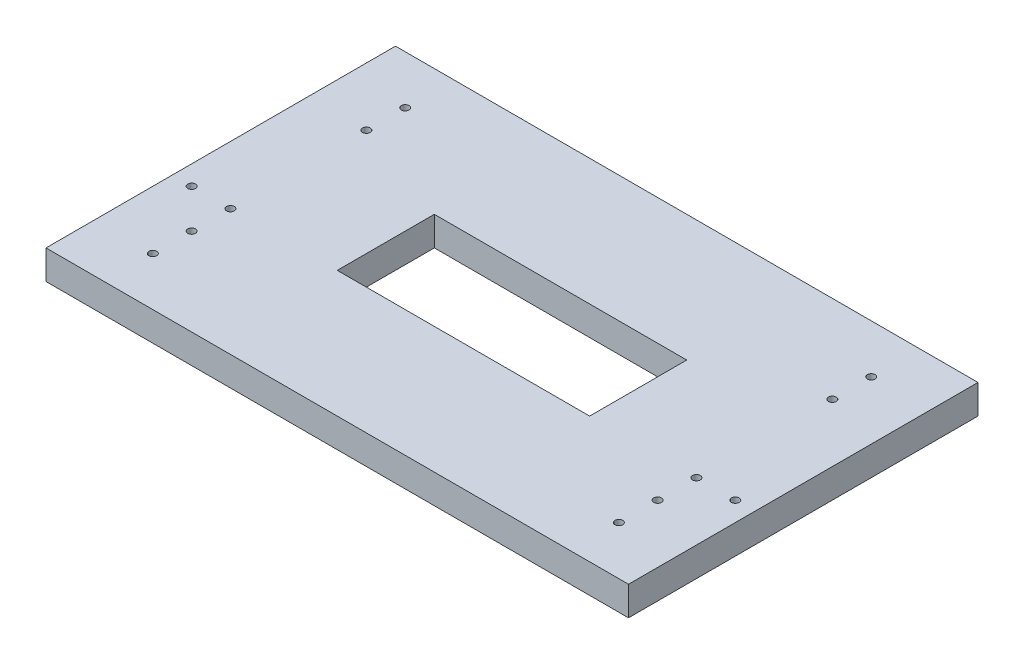
SolidWorks part; units mm, degrees
ref_plane "Alzado" through (0, 0, 0) normal (0, 0, 1) x (1, 0, 0)
ref_plane "Planta" through (0, 0, 0) normal (0, 1, 0) x (1, 0, 0)
ref_plane "Vista lateral" through (0, 0, 0) normal (1, 0, 0) x (0, 0, -1)
sketch "Croquis1" plane through (0, 0, 0) normal (0, 1, 0) x (1, 0, 0)
  line L1 (-150, -90) -> (150, -90)
  line L2 (-150, -90) -> (-150, 90)
  line L3 (-150, 90) -> (150, 90)
  line L4 (150, -90) -> (150, 90)
  line L5 (-150, -90) -> (150, 90) construction
  line L6 (-150, 90) -> (150, -90) construction
  point P0 (0, 0)
  dimension "D1" = 300
  dimension "D2" = 180
extrude "Saliente-Extruir1" add sketch "Croquis1" along normal blind 15
sketch "Croquis2" plane through (0, 15, 0) normal (0, 1, 0) x (1, 0, 0)
  line L0 (150, 90) -> (-150, 90) construction
  line L1 (-150, -90) -> (150, -90) construction
  line L2 (-150, 90) -> (-150, -90) construction
  line L3 (150, -90) -> (150, 90) construction
  circle A0 centre (-120, -45) radius 2
  circle A1 centre (-120, -65) radius 2
  circle A2 centre (120, -45) radius 2
  circle A3 centre (120, -65) radius 2
  circle A4 centre (-140, -25) radius 2
  circle A5 centre (-120, -25) radius 2
  circle A6 centre (120, -25) radius 2
  circle A7 centre (140, -25) radius 2
  circle A8 centre (-120, 65) radius 2
  circle A9 centre (-120, 45) radius 2
  circle A10 centre (120, 45) radius 2
  circle A11 centre (120, 65) radius 2
  dimension "D2" = 30
  dimension "D3" = 25
  dimension "D4" = 30
  dimension "D7" = 10
  dimension "D8" = 20
  dimension "D9" = 30
  dimension "D10" = 10
  dimension "D15" = 25
  dimension "D5" = 30
  dimension "D6" = 30
  dimension "D11" = 65
  dimension "D12" = 0
  dimension "D13" = 65
  dimension "D14" = 0
  dimension "D16" = 20
  dimension "D17" = 25
  dimension "D18" = 20
  dimension "D19" = 25
  dimension "D20" = 20
  dimension "D21" = 20
  dimension "D22" = 30
extrude "Cortar-Extruir1" cut sketch "Croquis2" against normal blind 10
sketch "Croquis3" plane through (0, 15, 0) normal (0, 1, 0) x (1, 0, 0)
  line L1 (-65, -25) -> (65, -25)
  line L2 (-65, -25) -> (-65, 25)
  line L3 (-65, 25) -> (65, 25)
  line L4 (65, -25) -> (65, 25)
  line L5 (-65, -25) -> (65, 25) construction
  line L6 (-65, 25) -> (65, -25) construction
  point P0 (0, 0)
extrude "Cortar-Extruir2" cut sketch "Croquis3" against normal up to surface (15 mm away) up to face at (0, 0, 0)
